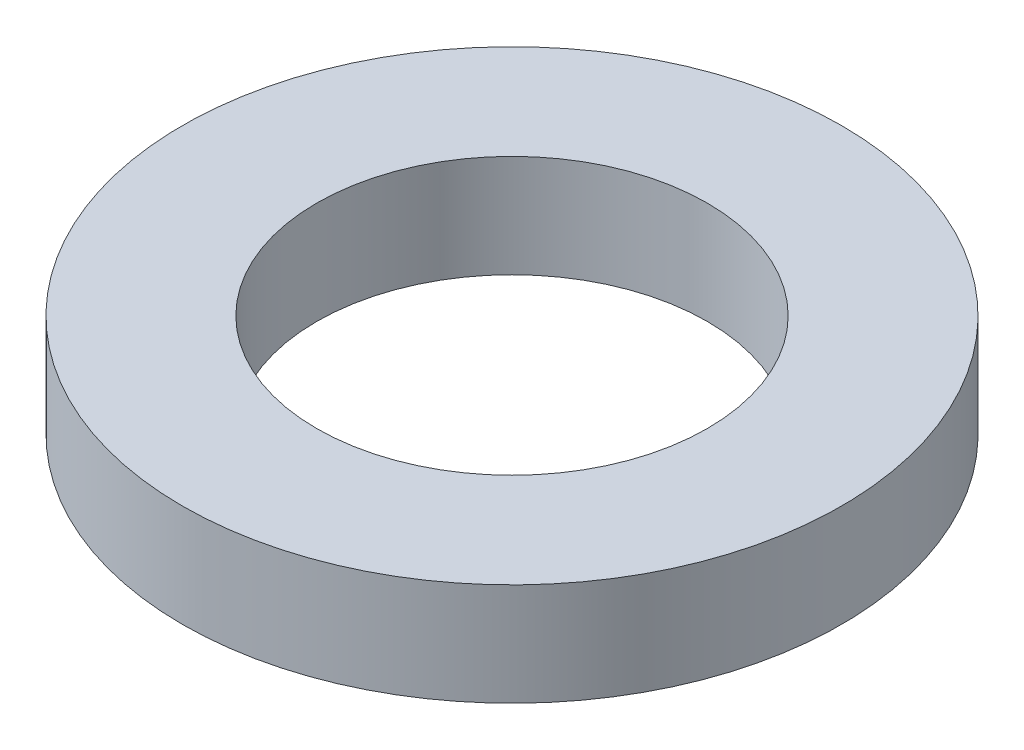
SolidWorks part; units mm, degrees
ref_plane "Front Plane" through (0, 0, 0) normal (0, 0, 1) x (1, 0, 0)
ref_plane "Top Plane" through (0, 0, 0) normal (0, 1, 0) x (1, 0, 0)
ref_plane "Right Plane" through (0, 0, 0) normal (1, 0, 0) x (0, 0, -1)
sketch "Sketch1" plane through (0, 0, 0) normal (0, 1, 0) x (1, 0, 0)
  circle A0 centre (0, 0) radius 67.5
  dimension "FLANGE_OD" = 135
extrude "Boss-Extrude1" add sketch "Sketch1" along normal blind 21
sketch "Sketch2" plane through (0, 0, 0) normal (0, 1, 0) x (1, 0, 0)
  circle A0 centre (0, 0) radius 40
  dimension "BORE_D" = 80
extrude "Cut-Extrude1" cut sketch "Sketch2" along normal through all
sketch "Sketch3" plane through (0, 21, 0) normal (0, 1, 0) x (1, 0, 0)
  circle A0 centre (0, 0) radius 22.9464 construction
  circle A1 centre (-22.9464, 0) radius 2.8409
  dimension "BOLT_D" = 5.6818
  dimension "BOLT_PCD" = 45.8928
extrude "Cut-Extrude2" cut sketch "Sketch3" against normal blind 18.4002 rebuild error yes
pattern_circular "CirPattern1" count 3 over 360 rebuild error yes
